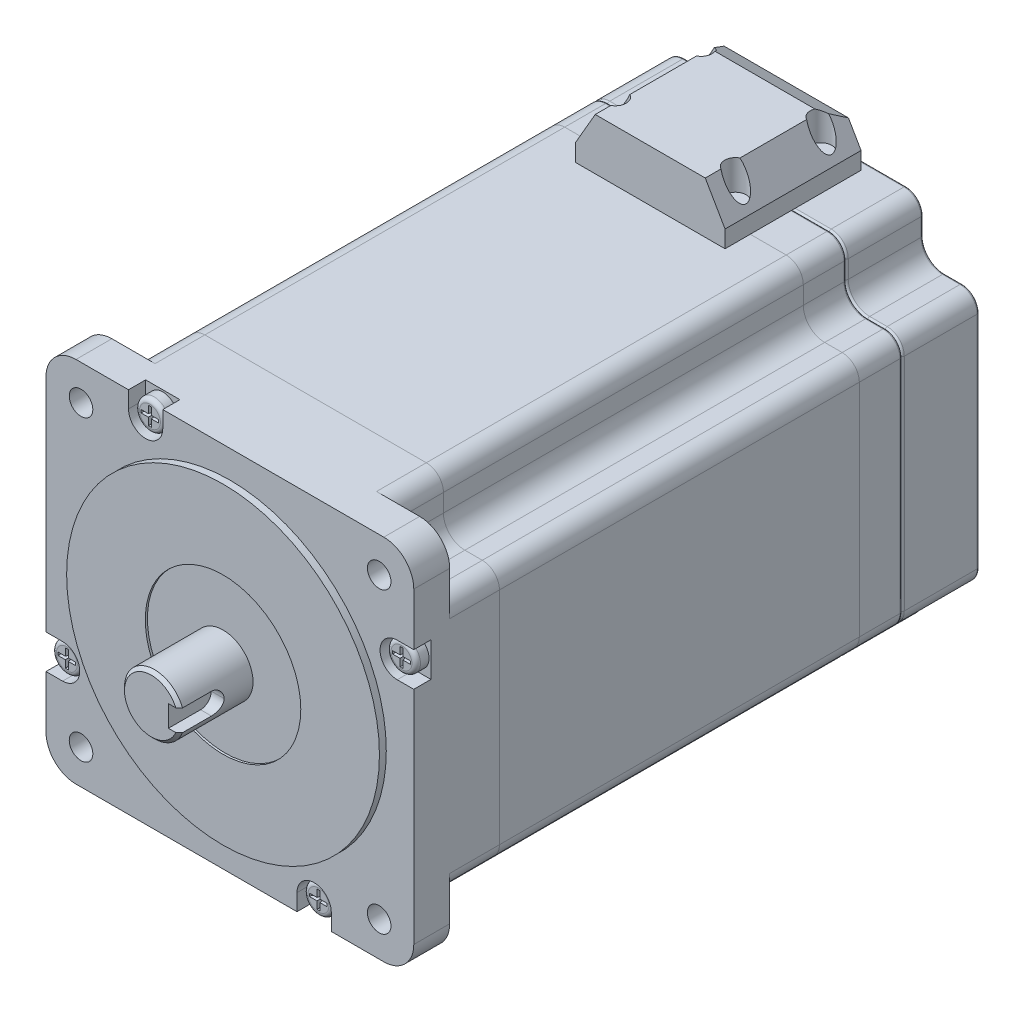
SolidWorks part; units mm, degrees
ref_plane "Front Plane" through (0, 0, 0) normal (0, 0, 1) x (1, 0, 0)
ref_plane "Top Plane" through (0, 0, 0) normal (0, 1, 0) x (1, 0, 0)
ref_plane "Right Plane" through (0, 0, 0) normal (1, 0, 0) x (0, 0, -1)
sketch "Sketch1" plane through (0, 0, 0) normal (0, 0, 1) x (1, 0, 0)
  line L0 (0, 42.925) -> (0, -42.925) construction
  line L1 (-35.925, -42.925) -> (35.925, -42.925)
  line L2 (-42.925, -35.925) -> (-42.925, 35.925)
  line L3 (-35.925, 42.925) -> (35.925, 42.925)
  line L4 (42.925, -35.925) -> (42.925, 35.925)
  line L5 (-42.925, -42.925) -> (42.925, 42.925) construction
  line L6 (-42.925, 42.925) -> (42.925, -42.925) construction
  circle A0 centre (-34.75, 34.75) radius 2.75
  circle A1 centre (34.847, 34.75) radius 2.75
  circle A2 centre (-34.75, -34.847) radius 2.75
  circle A3 centre (34.847, -34.847) radius 2.75
  arc A4 (35.925, -42.925) -> (42.925, -35.925) centre (35.925, -35.925) ccw
  arc A5 (-35.925, -42.925) -> (-42.925, -35.925) centre (-35.925, -35.925) cw
  arc A6 (35.925, 42.925) -> (42.925, 35.925) centre (35.925, 35.925) cw
  arc A7 (-42.925, 35.925) -> (-35.925, 42.925) centre (-35.925, 35.925) cw
  point P0 (0, 0)
  dimension "D3" = 5.5
  dimension "D4" = 69.597
  dimension "D5" = 69.597
  dimension "D6" = 34.75
  dimension "D8" = 7
  dimension "D1" = 85.85
  dimension "D2" = 85.85
  dimension "D7" = 34.75
extrude "Boss-Extrude1" add sketch "Sketch1" along normal blind 114
sketch "Sketch2" plane through (0, 0, 114) normal (0, 0, 1) x (1, 0, 0)
  circle A0 centre (0, 0) radius 36.51
  dimension "D1" = 73.02
extrude "Boss-Extrude2" add sketch "Sketch2" along normal blind 1.6
sketch "Sketch3" plane through (0, 0, 115.6) normal (0, 0, 1) x (1, 0, 0)
  circle A0 centre (0, 0) radius 7
  dimension "D1" = 14
extrude "Boss-Extrude3" add sketch "Sketch3" along normal blind 31.75 and the other way blind 5
sketch "Sketch4" plane through (0, 0, 147.35) normal (0, 0, 1) x (1, 0, 0)
  line L0 (0, 0) -> (13, 0) construction
  line L2 (9, -2.5) -> (4, -2.5)
  line L3 (9, -2.5) -> (9, 2.5)
  line L4 (9, 2.5) -> (4, 2.5)
  line L5 (4, -2.5) -> (4, 2.5)
  line L6 (9, -2.5) -> (4, 2.5) construction
  line L7 (9, 2.5) -> (4, -2.5) construction
  circle A0 centre (0, 0) radius 7 construction
  point P3 (6.5, 0)
  dimension "D1" = 5
  dimension "D2" = 11
  dimension "D3" = 5
extrude "Cut-Extrude1" cut sketch "Sketch4" against normal blind 25
fillet "Fillet1" radius 2.5 2 edges at (5.2692, -2.5, 122.35) (5.2692, 2.5, 122.35)
chamfer "Chamfer1" distance 0.5 angle 45 1 edges at (-7, 0, 147.35)
sketch "Sketch5" plane through (0, 0, 115.6) normal (0, 0, 1) x (1, 0, 0)
  circle A0 centre (0, 0) radius 18.1505
extrude "Cut-Extrude2" cut sketch "Sketch5" against normal blind 0.5
sketch "Sketch6" plane through (0, 0, 0) normal (0, 0, -1) x (-1, 0, 0)
  line L0 (0, 42.925) -> (0, -42.925) construction
  line L1 (-35.925, 42.925) -> (35.925, 42.925) construction
  line L2 (35.925, -42.925) -> (-35.925, -42.925) construction
  line L3 (-42.925, 0) -> (42.925, 0) construction
  line L4 (-42.925, -35.925) -> (-42.925, 35.925) construction
  line L5 (42.925, 35.925) -> (42.925, -35.925) construction
  line L6 (-29.847, 34.75) -> (-29.847, 42.925)
  line L7 (-34.847, 29.75) -> (-42.925, 29.75)
  line L8 (-42.925, 35.925) -> (-42.925, 29.75)
  line L9 (-35.925, 42.925) -> (-29.847, 42.925)
  line L10 (35.925, 42.925) -> (29.847, 42.925)
  line L11 (42.925, 35.925) -> (42.925, 29.75)
  line L12 (34.847, 29.75) -> (42.925, 29.75)
  line L13 (29.847, 34.75) -> (29.847, 42.925)
  line L14 (29.847, -34.75) -> (29.847, -42.925)
  line L15 (34.847, -29.75) -> (42.925, -29.75)
  line L16 (42.925, -35.925) -> (42.925, -29.75)
  line L17 (35.925, -42.925) -> (29.847, -42.925)
  line L18 (-35.925, -42.925) -> (-29.847, -42.925)
  line L19 (-42.925, -35.925) -> (-42.925, -29.75)
  line L20 (-34.847, -29.75) -> (-42.925, -29.75)
  line L21 (-29.847, -34.75) -> (-29.847, -42.925)
  arc A0 (-34.847, 29.75) -> (-29.847, 34.75) centre (-34.847, 34.75) ccw
  arc A2 (-35.925, 42.925) -> (-42.925, 35.925) centre (-35.925, 35.925) ccw
  arc A3 (35.925, 42.925) -> (42.925, 35.925) centre (35.925, 35.925) cw
  arc A4 (34.847, 29.75) -> (29.847, 34.75) centre (34.847, 34.75) cw
  arc A5 (34.847, -29.75) -> (29.847, -34.75) centre (34.847, -34.75) ccw
  arc A6 (35.925, -42.925) -> (42.925, -35.925) centre (35.925, -35.925) ccw
  arc A7 (-35.925, -42.925) -> (-42.925, -35.925) centre (-35.925, -35.925) cw
  arc A8 (-34.847, -29.75) -> (-29.847, -34.75) centre (-34.847, -34.75) cw
  dimension "D1" = 10
extrude "Cut-Extrude3" cut sketch "Sketch6" against normal offset from surface (105.62 mm away) 8.38 up to face at (37.597, -34.847, 114)
sketch "Sketch7" plane through (0, 42.925, 0) normal (0, 1, 0) x (1, 0, 0)
  line L0 (-68.5991, -94) -> (62.7234, -94)
  line L1 (-68.5991, -10) -> (56.8477, -10)
  line L2 (29.847, 0) -> (-29.847, 0) construction
  line L3 (35.925, -114) -> (-35.925, -114) construction
  dimension "D1" = 10
  dimension "D2" = 20
split line "Split Line3"
fillet "Fillet2" radius 0.5 16 edges at (38.886, 29.75, 0) (31.3115, 31.2145, 0) (29.847, 38.8375, 0) (0, 42.925, 0) (-29.847, 38.8375, 0) (-31.3115, 31.2145, 0) (-38.886, 29.75, 0) (-42.925, 0, 0) (-38.886, -29.75, 0) (-31.3115, -31.2145, 0) (-29.847, -38.8375, 0) (0, -42.925, 0) (29.847, -38.8375, 0) (31.3115, -31.2145, 0) (38.886, -29.75, 0) (42.925, 0, 0)
fillet "Fillet3" radius 4 32 edges at (-29.7005, -42.7786, 0.1464) (-42.7786, -29.6036, 0.1464) (-42.7786, 29.6036, 0.1464) (-29.7005, 42.7786, 0.1464) (29.7005, 42.7786, 0.1464) (42.7786, 29.6036, 0.1464) (42.7786, -29.6036, 0.1464) (29.7005, -42.7786, 0.1464) (29.847, -42.925, 99.81) (29.847, -42.925, 52) (29.847, -42.925, 5.25) (42.925, -29.75, 99.81) (42.925, -29.75, 52) (42.925, -29.75, 5.25) (42.925, 29.75, 99.81) (42.925, 29.75, 52) (42.925, 29.75, 5.25) (29.847, 42.925, 99.81) (29.847, 42.925, 52) (29.847, 42.925, 5.25) (-29.847, 42.925, 99.81) (-29.847, 42.925, 52) (-29.847, 42.925, 5.25) (-42.925, 29.75, 99.81) (-42.925, 29.75, 52) (-42.925, 29.75, 5.25) (-42.925, -29.75, 99.81) (-42.925, -29.75, 52) (-42.925, -29.75, 5.25) (-29.847, -42.925, 99.81) (-29.847, -42.925, 5.25) (-29.847, -42.925, 52)
sketch "Sketch8" plane through (0, 0, 0) normal (0, 0, -1) x (-1, 0, 0)
  circle A0 centre (0, 0) radius 10
  dimension "D1" = 20
extrude "Cut-Extrude4" cut sketch "Sketch8" against normal blind 1
sketch "Sketch9" plane through (0, 0, 1) normal (0, 0, -1) x (-1, 0, 0)
  circle A0 centre (0, 0) radius 6
  dimension "D1" = 12
extrude "Boss-Extrude4" add sketch "Sketch9" along normal blind 0.8 separate body
sketch "Sketch10" plane through (0, 0, 114) normal (0, 0, 1) x (1, 0, 0)
  line L0 (-23.6682, 39.0569) -> (-23.6682, 42.925)
  line L1 (35.925, 42.925) -> (-35.925, 42.925) construction
  line L2 (-23.6682, 42.925) -> (-15.6682, 42.925)
  line L3 (-15.6682, 42.925) -> (-15.6682, 39.0569)
  line L4 (39.0569, 23.6682) -> (42.925, 23.6682)
  line L5 (42.925, 23.6682) -> (42.925, 15.6682)
  line L6 (42.925, 15.6682) -> (39.0569, 15.6682)
  line L7 (23.6682, -39.0569) -> (23.6682, -42.925)
  line L8 (23.6682, -42.925) -> (15.6682, -42.925)
  line L9 (15.6682, -42.925) -> (15.6682, -39.0569)
  line L10 (-39.0569, -23.6682) -> (-42.925, -23.6682)
  line L11 (-42.925, -23.6682) -> (-42.925, -15.6682)
  line L12 (-42.925, -15.6682) -> (-39.0569, -15.6682)
  arc A0 (-23.6682, 39.0569) -> (-15.6682, 39.0569) centre (-19.6682, 39.0569) ccw
  arc A1 (39.0569, 23.6682) -> (39.0569, 15.6682) centre (39.0569, 19.6682) ccw
  arc A2 (23.6682, -39.0569) -> (15.6682, -39.0569) centre (19.6682, -39.0569) ccw
  arc A3 (-39.0569, -23.6682) -> (-39.0569, -15.6682) centre (-39.0569, -19.6682) ccw
  point P25 (0, 0)
  dimension "D1" = 8
  dimension "D2" = 4
extrude "Cut-Extrude5" cut sketch "Sketch10" against normal blind 4
sketch "Sketch11" plane through (0, 0, 110) normal (0, 0, 1) x (1, 0, 0)
  circle A0 centre (-19.6682, 39.0569) radius 3.4342
  point P12 (0, 0)
extrude "Boss-Extrude5" add sketch "Sketch11" along normal blind 3 separate body
fillet "Fillet4" radius 1 1 edges at (-16.234, 39.0569, 113)
sketch "Sketch12" plane through (0, 0, 113) normal (0, 0, 1) x (1, 0, 0)
  line L0 (-19.3179, 39.4068) -> (-17.6111, 39.4068)
  line L1 (-20.0186, 36.9976) -> (-19.3179, 36.9976)
  line L2 (-20.0186, 36.9976) -> (-20.0186, 38.7069)
  line L3 (-20.0186, 41.1161) -> (-19.3179, 41.1161)
  line L4 (-19.3179, 36.9976) -> (-19.3179, 38.7069)
  line L5 (-20.0186, 36.9976) -> (-19.3179, 41.1161) construction
  line L6 (-20.0186, 41.1161) -> (-19.3179, 36.9976) construction
  line L7 (-21.7254, 39.4068) -> (-20.0186, 39.4068)
  line L8 (-21.7254, 39.4068) -> (-21.7254, 38.7069)
  line L9 (-21.7254, 38.7069) -> (-20.0186, 38.7069)
  line L10 (-17.6111, 39.4068) -> (-17.6111, 38.7069)
  line L11 (-21.7254, 39.4068) -> (-17.6111, 38.7069) construction
  line L12 (-21.7254, 38.7069) -> (-17.6111, 39.4068) construction
  line L13 (-19.3179, 38.7069) -> (-17.6111, 38.7069)
  line L14 (-20.0186, 39.4068) -> (-20.0186, 41.1161)
  line L15 (-19.3179, 39.4068) -> (-19.3179, 41.1161)
  point P0 (-19.6682, 39.0569)
  point P6 (-19.6682, 39.0569)
extrude "Cut-Extrude6" cut sketch "Sketch12" against normal blind 2 draft 6
chamfer "Chamfer2" distance 1.5 angle 45 4 edges at (-19.6682, 37.2078, 111) (-19.6682, 40.9059, 111) (-17.8213, 39.0569, 111) (-21.5151, 39.0569, 111) first distance on face at (-19.6682, 37.1027, 112) first distance on face at (-19.6682, 41.011, 112) first distance on face at (-17.7162, 39.0569, 112) first distance on face at (-21.6202, 39.0569, 112)
pattern_circular "CirPattern3" count 4 over 360 about axis through (0, 0, 114) along (0, 0, 1) of bodies 115
sketch "Sketch14" plane through (0, 0, 0) normal (0, 0, -1) x (-1, 0, 0)
  line L0 (-25.847, 42.925) -> (25.847, 42.925) construction
  line L1 (29.847, 38.925) -> (29.847, 34.75) construction
  line L2 (-29.847, 34.75) -> (-29.847, 38.925) construction
  line L3 (-38.925, 29.75) -> (-34.847, 29.75) construction
  line L4 (-42.925, -25.75) -> (-42.925, 25.75) construction
  line L5 (34.847, 29.75) -> (38.925, 29.75) construction
  line L6 (42.925, 25.75) -> (42.925, -25.75) construction
  line L7 (-34.847, -29.75) -> (-38.925, -29.75) construction
  line L8 (-29.847, -38.925) -> (-29.847, -34.75) construction
  line L9 (25.847, -42.925) -> (-25.847, -42.925) construction
  line L10 (38.925, -29.75) -> (34.847, -29.75) construction
  line L11 (29.847, -34.75) -> (29.847, -38.925) construction
  line L12 (-25.847, 42.925) -> (25.847, 42.925)
  line L13 (29.847, 38.925) -> (29.847, 34.75)
  line L14 (-29.847, 34.75) -> (-29.847, 38.925)
  line L15 (-38.925, 29.75) -> (-34.847, 29.75)
  line L16 (-42.925, -25.75) -> (-42.925, 25.75)
  line L17 (34.847, 29.75) -> (38.925, 29.75)
  line L18 (42.925, 25.75) -> (42.925, -25.75)
  line L19 (-34.847, -29.75) -> (-38.925, -29.75)
  line L20 (-29.847, -38.925) -> (-29.847, -34.75)
  line L21 (25.847, -42.925) -> (-25.847, -42.925)
  line L22 (38.925, -29.75) -> (34.847, -29.75)
  line L23 (29.847, -34.75) -> (29.847, -38.925)
  arc A0 (29.847, 34.75) -> (34.847, 29.75) centre (34.847, 34.75) ccw construction
  arc A1 (29.847, 38.925) -> (25.847, 42.925) centre (25.847, 38.925) ccw construction
  arc A2 (-25.847, 42.925) -> (-29.847, 38.925) centre (-25.847, 38.925) ccw construction
  arc A3 (-34.847, 29.75) -> (-29.847, 34.75) centre (-34.847, 34.75) ccw construction
  arc A4 (-38.925, 29.75) -> (-42.925, 25.75) centre (-38.925, 25.75) ccw construction
  arc A5 (42.925, 25.75) -> (38.925, 29.75) centre (38.925, 25.75) ccw construction
  arc A6 (-42.925, -25.75) -> (-38.925, -29.75) centre (-38.925, -25.75) ccw construction
  arc A7 (-29.847, -34.75) -> (-34.847, -29.75) centre (-34.847, -34.75) ccw construction
  arc A8 (-29.847, -38.925) -> (-25.847, -42.925) centre (-25.847, -38.925) ccw construction
  arc A9 (38.925, -29.75) -> (42.925, -25.75) centre (38.925, -25.75) ccw construction
  arc A10 (34.847, -29.75) -> (29.847, -34.75) centre (34.847, -34.75) ccw construction
  arc A11 (25.847, -42.925) -> (29.847, -38.925) centre (25.847, -38.925) ccw construction
  arc A12 (29.847, 34.75) -> (34.847, 29.75) centre (34.847, 34.75) ccw
  arc A13 (29.847, 38.925) -> (25.847, 42.925) centre (25.847, 38.925) ccw
  arc A14 (-25.847, 42.925) -> (-29.847, 38.925) centre (-25.847, 38.925) ccw
  arc A15 (-34.847, 29.75) -> (-29.847, 34.75) centre (-34.847, 34.75) ccw
  arc A16 (-38.925, 29.75) -> (-42.925, 25.75) centre (-38.925, 25.75) ccw
  arc A17 (42.925, 25.75) -> (38.925, 29.75) centre (38.925, 25.75) ccw
  arc A18 (-42.925, -25.75) -> (-38.925, -29.75) centre (-38.925, -25.75) ccw
  arc A19 (-29.847, -34.75) -> (-34.847, -29.75) centre (-34.847, -34.75) ccw
  arc A20 (-29.847, -38.925) -> (-25.847, -42.925) centre (-25.847, -38.925) ccw
  arc A21 (38.925, -29.75) -> (42.925, -25.75) centre (38.925, -25.75) ccw
  arc A22 (34.847, -29.75) -> (29.847, -34.75) centre (34.847, -34.75) ccw
  arc A23 (25.847, -42.925) -> (29.847, -38.925) centre (25.847, -38.925) ccw
extrude "Boss-Extrude6" add sketch "Sketch14" along normal blind 18
fillet "Fillet6" radius 0.5 48 edges at (28.6754, 41.7534, 0) (0, 42.925, 0) (-28.6754, 41.7534, 0) (-29.847, 36.8375, 0) (-31.3115, 31.2145, 0) (-36.886, 29.75, 0) (-41.7534, 28.5784, 0) (-42.925, 0, 0) (-41.7534, -28.5784, 0) (-36.886, -29.75, 0) (-31.3115, -31.2145, 0) (-29.847, -36.8375, 0) (-28.6754, -41.7534, 0) (0, -42.925, 0) (28.6754, -41.7534, 0) (29.847, -36.8375, 0) (31.3115, -31.2145, 0) (36.886, -29.75, 0) (41.7534, -28.5784, 0) (42.925, 0, 0) (41.7534, 28.5784, 0) (36.886, 29.75, 0) (31.3115, 31.2145, 0) (31.3115, 31.2145, -18) (36.886, 29.75, -18) (41.7534, 28.5784, -18) (42.925, 0, -18) (41.7534, -28.5784, -18) (36.886, -29.75, -18) (31.3115, -31.2145, -18) (29.847, -36.8375, -18) (28.6754, -41.7534, -18) (0, -42.925, -18) (-28.6754, -41.7534, -18) (-29.847, -36.8375, -18) (-31.3115, -31.2145, -18) (-36.886, -29.75, -18) (-41.7534, -28.5784, -18) (-42.925, 0, -18) (-41.7534, 28.5784, -18) (-36.886, 29.75, -18) (-31.3115, 31.2145, -18) (-29.847, 36.8375, -18) (-28.6754, 41.7534, -18) (0, 42.925, -18) (28.6754, 41.7534, -18) (29.847, 36.8375, 0) (29.847, 36.8375, -18)
sketch "Sketch15" plane through (0, 0, 147.35) normal (0, 0, 1) x (1, 0, 0)
  circle A0 centre (0, 0) radius 10
  dimension "D1" = 20
extrude "Cut-Extrude7" cut sketch "Sketch15" against normal blind 15
chamfer "Chamfer3" distance 0.75 angle 45 1 edges at (-7, 0, 132.35)
sketch "Sketch16" plane through (0, 42.925, 0) normal (0, -1, 0) x (0, 0, 1)
  line L1 (15.875, -17.4625) -> (-15.875, -17.4625)
  line L2 (15.875, -17.4625) -> (15.875, 17.4625)
  line L3 (15.875, 17.4625) -> (-15.875, 17.4625)
  line L4 (-15.875, -17.4625) -> (-15.875, 17.4625)
  line L5 (15.875, -17.4625) -> (-15.875, 17.4625) construction
  line L6 (15.875, 17.4625) -> (-15.875, -17.4625) construction
  point P0 (0, 0)
  dimension "D1" = 31.75
  dimension "D2" = 34.925
extrude "Boss-Extrude7" add sketch "Sketch16" against normal blind 12
chamfer "Chamfer4" distance 8 angle 30 2 edges at (17.4625, 54.925, 0) (-17.4625, 54.925, 0) first distance on face at (17.4625, 46.3536, 1.4286) first distance on face at (-17.4625, 46.3536, 1.4286)
chamfer "Chamfer5" distance 5 angle 30 1 edges at (0, 54.925, -15.875) first distance on face at (0, 54.925, 0)
sketch "Sketch17" plane through (0, 54.925, 0) normal (0, 1, 0) x (0, 0, 1)
  line L1 (-10, 14) -> (10, 14) construction
  line L2 (-10, 14) -> (-10, -14) construction
  line L3 (-10, -14) -> (10, -14) construction
  line L4 (10, 14) -> (10, -14) construction
  line L5 (-10, 14) -> (10, -14) construction
  line L6 (-10, -14) -> (10, 14) construction
  circle A0 centre (-10, 14) radius 2.5
  circle A1 centre (-10, -14) radius 2.5
  circle A2 centre (10, -14) radius 2.5
  circle A3 centre (10, 14) radius 2.5
  point P0 (0, 0)
  dimension "D3" = 5
  dimension "D1" = 28
  dimension "D2" = 20
extrude "Cut-Extrude8" cut sketch "Sketch17" against normal blind 7
